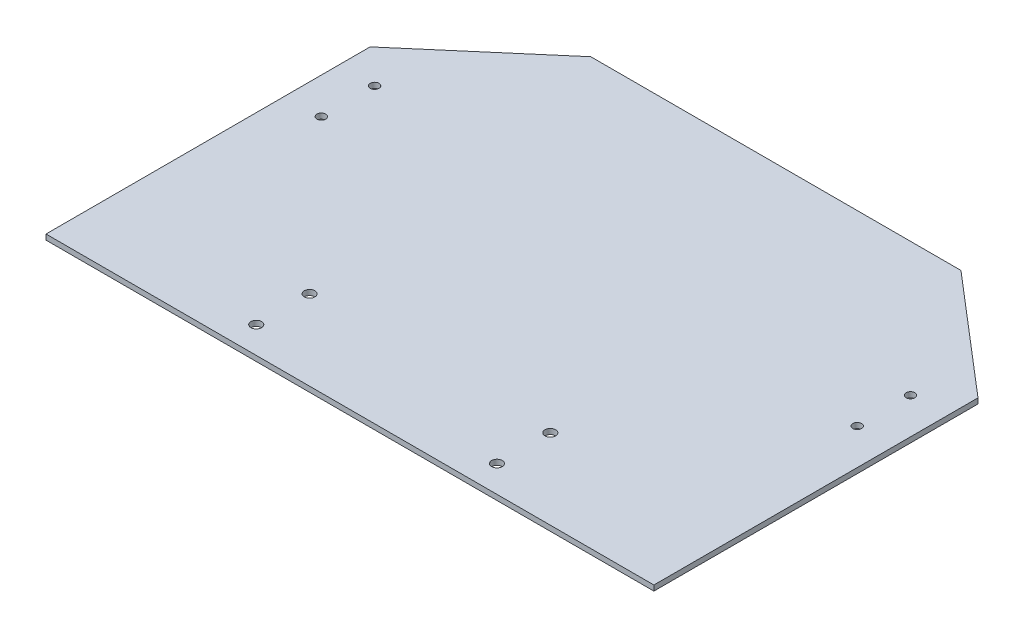
SolidWorks part; units mm, degrees
material "Nylon "
ref_plane "Plano frontal" through (0, 0, 0) normal (0, 0, 1) x (1, 0, 0)
ref_plane "Plano superior" through (0, 0, 0) normal (0, 1, 0) x (1, 0, 0)
ref_plane "Plano direito" through (0, 0, 0) normal (1, 0, 0) x (0, 0, -1)
sketch "Esboço1" plane through (0, 0, 0) normal (0, 1, 0) x (1, 0, 0)
  line L0 (-114, -79.875) -> (114, -79.875)
  line L1 (0, 79.875) -> (0, -79.875)
  line L2 (114, -79.875) -> (114, 41.685)
  line L3 (-69.415, 79.875) -> (69.415, 79.875)
  line L4 (69.415, 79.875) -> (114, 41.685)
  line L5 (-114, -79.875) -> (-114, 41.685)
  line L7 (-69.415, 79.875) -> (-114, 41.685)
  line L8 (51.996, -79.875) -> (51.996, -113.875)
  line L9 (51.996, -113.875) -> (114, -79.875)
  line L10 (-51, -79.875) -> (-51, -113.875)
  line L11 (-51, -113.875) -> (-114, -79.875)
  point P6 (114, -19.095)
  point P7 (0, 0)
  dimension "D1" = 228
  dimension "D2" = 159.75
  dimension "D3" = 121.56
  dimension "D4" = 138.83
  dimension "D5" = 63
  dimension "D6" = 62.004
  dimension "D7" = 34
  dimension "D8" = 34
extrude "Ressalto-extrusão1" add sketch "Esboço1" along normal blind 2 contours L3 L7 L5 L0 L1 | L4 L3 L1 L0 L2 region at (-54.9335, 0, 3.2928) region at (54.9335, 0, 3.2928)
ref_plane "Plano1" through (0, 0, -79.875) normal (0, 0, -1) x (-1, 0, 0)
sketch "Esboço3" plane through (0, 2, 0) normal (0, 1, 0) x (1, 0, 0)
  line L0 (-114, -79.875) -> (-114, 41.685) construction
  line L1 (-114, -79.875) -> (114, -79.875) construction
  line L2 (114, -79.875) -> (114, 41.685) construction
  line L5 (0, -1000) -> (0, 49000) construction
  circle A0 centre (-45.14, -69.875) radius 2
  circle A1 centre (45.14, -69.875) radius 2
  circle A3 centre (-45.14, -49.875) radius 2
  circle A4 centre (45.14, -49.875) radius 2
  point P0 (-45.14, -69.875)
  point P5 (45.14, -69.875)
  dimension "D3" = 4
  dimension "D5" = 4
  dimension "D7" = 20
  dimension "D1" = 68.86
  dimension "D2" = 10
  dimension "D4" = 68.86
  dimension "D6" = 10
extrude "Corte-extrusão2" cut sketch "Esboço3" against normal blind 10
sketch "Esboço4" plane through (0, 2, 0) normal (0, 1, 0) x (1, 0, 0)
  line L8 (-114, -79.875) -> (114, -79.875) construction
  line L10 (-114, 41.685) -> (-114, -79.875)
  line L11 (-114, -79.875) -> (-102.536, -79.875)
  line L12 (-102.536, 75.0881) -> (-102.536, -79.875)
  line L13 (-102.536, 75.0881) -> (-102.536, 86.6244)
  line L15 (114, 41.685) -> (114, -79.875)
  line L16 (114, -79.875) -> (100.6429, -79.875)
  line L17 (100.6429, 75.0881) -> (100.6429, -79.875)
  line L18 (-102.536, 86.6244) -> (-114, 41.685)
  line L19 (100.6429, 75.0881) -> (100.6429, 88.8016)
  line L20 (100.6429, 88.8016) -> (114, 41.685)
extrude "Corte-extrusão4" [suppressed] cut sketch "Esboço4" against normal blind 10
move or copy body "Corpo-Converter em corpo de malha1" [suppressed] bodies to move or copy 110 copy no translate (0, 0, 0) parameters "D1"=0, "D2"=0, "D3"=0
sketch "Esboço5" plane through (0, 2, 0) normal (0, 1, 0) x (1, 0, 0)
  circle A0 centre (100.5, 29.877) radius 1.65
  circle A1 centre (100.5, 9.877) radius 1.65
  circle A2 centre (100.5, 9.877) radius 1.65 construction
  circle A3 centre (100.5, 29.877) radius 1.65 construction
  circle A4 centre (-100.5, 29.877) radius 1.65
  circle A5 centre (-100.5, 9.877) radius 1.65
  circle A6 centre (-100.5, 29.877) radius 1.65 construction
  circle A7 centre (-100.5, 9.877) radius 1.65 construction
extrude "Corte-extrusão5" cut sketch "Esboço5" against normal blind 2
